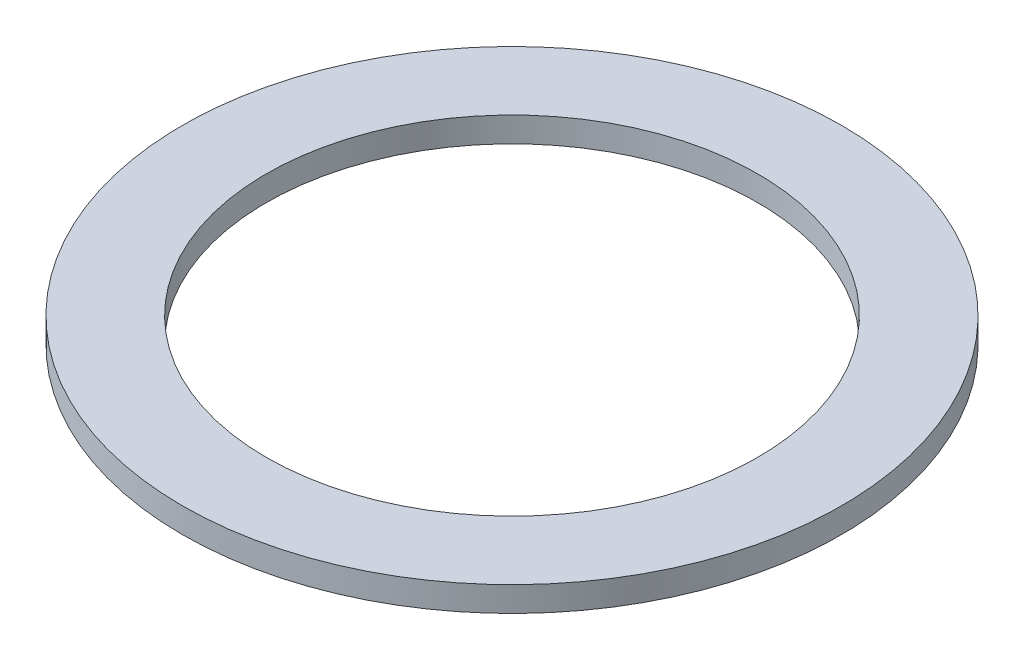
SolidWorks part; units mm, degrees
material "1060 Alloy"
ref_plane "Front Plane" through (0, 0, 0) normal (0, 0, 1) x (1, 0, 0)
ref_plane "Top Plane" through (0, 0, 0) normal (0, 1, 0) x (1, 0, 0)
ref_plane "Right Plane" through (0, 0, 0) normal (1, 0, 0) x (0, 0, -1)
sketch "Sketch1" plane through (0, 0, 0) normal (0, 1, 0) x (1, 0, 0)
  circle A0 centre (0, 0) radius 66
  circle A1 centre (0, 0) radius 49.2
  circle A2 centre (0, 0) radius 76.2 construction
  dimension "D1" = 152.4
  dimension "D2" = 98.4
  dimension "D3" = 132
extrude "Boss-Extrude1" add sketch "Sketch1" along normal blind 5
